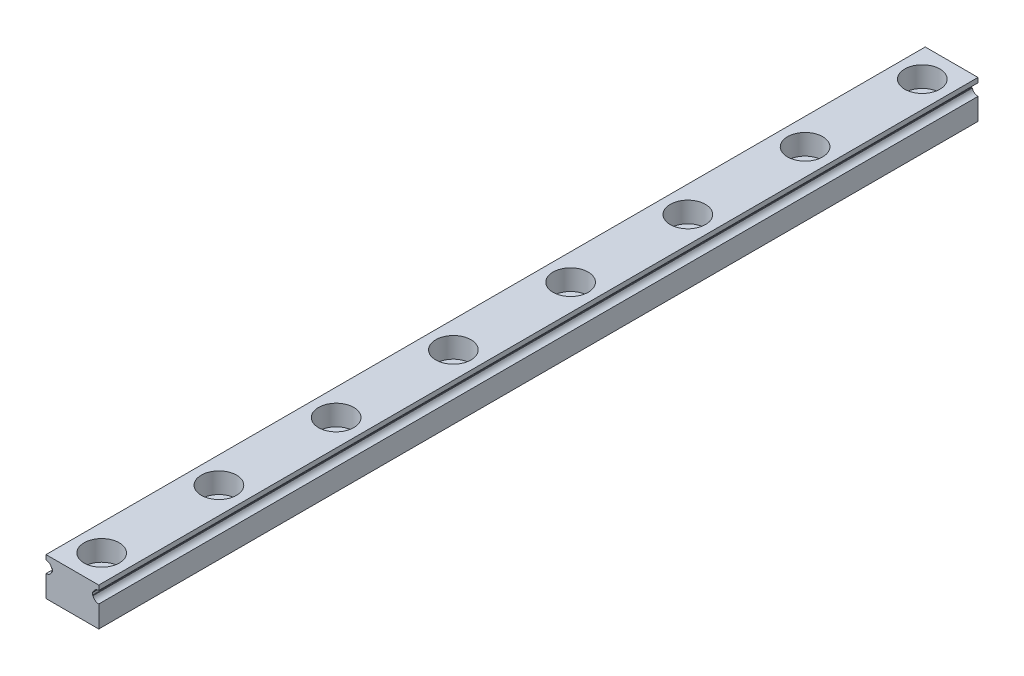
SolidWorks part; units mm, degrees
material "6061 合金"
ref_plane "Спереди" through (0, 0, 0) normal (0, 0, 1) x (1, 0, 0)
ref_plane "Сверху" through (0, 0, 0) normal (0, 1, 0) x (1, 0, 0)
ref_plane "Справа" through (0, 0, 0) normal (1, 0, 0) x (0, 0, -1)
sketch "Sketch1" plane through (0, 0, 0) normal (0, 0, 1) x (1, 0, 0)
  line L0 (0, 0) -> (0, 5.7299) construction
  line L1 (-4.5, -3.25) -> (4.5, -3.25)
  line L2 (-4.5, -3.25) -> (-4.5, 0.45)
  line L3 (-4.5, 3.25) -> (4.5, 3.25)
  line L4 (4.5, -3.25) -> (4.5, 0.45)
  line L5 (-4.5, -3.25) -> (4.5, 3.25) construction
  line L6 (-4.5, 3.25) -> (4.5, -3.25) construction
  line L7 (-4.5, 2.45) -> (-4.5, 3.25)
  line L8 (-3.5318, 1.2) -> (-3.4, 1.2)
  line L9 (3.5318, 1.2) -> (3.4, 1.2)
  line L10 (-3.5318, 1.7) -> (-3.4, 1.7)
  line L11 (-3.4, 1.2) -> (-3.4, 1.7)
  line L12 (3.4, 1.2) -> (3.4, 1.7)
  line L13 (3.5318, 1.7) -> (3.4, 1.7)
  line L14 (4.5, 2.45) -> (4.5, 3.25)
  line L15 (-3.4, 1.45) -> (-4.5, 1.45) construction
  arc A0 (-3.5318, 1.7) -> (-4.5, 2.45) centre (-4.5, 1.45) ccw
  arc A1 (-4.5, 0.45) -> (-3.5318, 1.2) centre (-4.5, 1.45) ccw
  arc A2 (4.5, 0.45) -> (3.5318, 1.2) centre (4.5, 1.45) cw
  arc A3 (3.5318, 1.7) -> (4.5, 2.45) centre (4.5, 1.45) cw
  point P0 (0, 0)
  dimension "D3" = 1
  dimension "D1" = 9
  dimension "D2" = 6.5
  dimension "D4" = 2.05
  dimension "D5" = 6.8
  dimension "D6" = 0.5
extrude "Extrude1" add sketch "Sketch1" along normal blind 150
sketch "Sketch2" plane through (0, 3.25, 0) normal (0, 1, 0) x (1, 0, 0)
  line L0 (4.5, 0) -> (-4.5, 0) construction
  circle A0 centre (0, -5) radius 1.75
  circle A1 centre (0, -5) radius 3
  dimension "D1" = 3.5
  dimension "D2" = 6
  dimension "D3" = 5
extrude "Extrude2" cut sketch "Sketch2" against normal blind 3.5 contours A1
extrude "Extrude3" cut sketch "Sketch" against normal through all contours A0
sketch "Sketch" plane through (0, 3.25, 0) normal (0, 1, 0) x (1, 0, 0) same geometry as "Sketch2"
pattern_linear "LPattern1" count 40 spacing 20 along (0, 0, 1) of "Extrude2", "Extrude3"
chamfer "Chamfer1" [suppressed] distance 0.3 angle 45
sketch "草图1" [suppressed] plane through (0, 0, 200) normal (0, 0, 1) x (1, 0, 0)
  line L12 (4.5, 2.45) -> (4.5, 3.25)
  line L13 (4.5, 3.25) -> (-4.5, 3.25)
  line L14 (-4.5, 3.25) -> (-4.5, 2.45)
  line L15 (-3.5318, 1.7) -> (-3.4, 1.7)
  line L16 (-3.4, 1.7) -> (-3.4, 1.2)
  line L17 (-3.4, 1.2) -> (-3.5318, 1.2)
  line L18 (-4.5, 0.45) -> (-4.5, -3.25)
  line L19 (-4.5, -3.25) -> (4.5, -3.25)
  line L20 (4.5, -3.25) -> (4.5, 0.45)
  line L21 (3.5318, 1.2) -> (3.4, 1.2)
  line L22 (3.4, 1.2) -> (3.4, 1.7)
  line L23 (3.4, 1.7) -> (3.5318, 1.7)
  line L24 (4.5, 2.45) -> (4.5, 3.25)
  line L25 (4.5, 3.25) -> (-4.5, 3.25)
  line L26 (-4.5, 3.25) -> (-4.5, 2.45)
  line L27 (-3.5318, 1.7) -> (-3.4, 1.7)
  line L28 (-3.4, 1.7) -> (-3.4, 1.2)
  line L29 (-3.4, 1.2) -> (-3.5318, 1.2)
  line L30 (-4.5, 0.45) -> (-4.5, -3.25)
  line L31 (-4.5, -3.25) -> (4.5, -3.25)
  line L32 (4.5, -3.25) -> (4.5, 0.45)
  line L33 (3.5318, 1.2) -> (3.4, 1.2)
  line L34 (3.4, 1.2) -> (3.4, 1.7)
  line L35 (3.4, 1.7) -> (3.5318, 1.7)
  arc A4 (-3.5318, 1.7) -> (-4.5, 2.45) centre (-4.5, 1.45) ccw
  arc A5 (-4.5, 0.45) -> (-3.5318, 1.2) centre (-4.5, 1.45) ccw
  arc A6 (3.5318, 1.2) -> (4.5, 0.45) centre (4.5, 1.45) ccw
  arc A7 (4.5, 2.45) -> (3.5318, 1.7) centre (4.5, 1.45) ccw
  arc A8 (-3.5318, 1.7) -> (-4.5, 2.45) centre (-4.5, 1.45) ccw
  arc A9 (-4.5, 0.45) -> (-3.5318, 1.2) centre (-4.5, 1.45) ccw
  arc A10 (3.5318, 1.2) -> (4.5, 0.45) centre (4.5, 1.45) ccw
  arc A11 (4.5, 2.45) -> (3.5318, 1.7) centre (4.5, 1.45) ccw
  dimension "D1" = 0
extrude "切除-拉伸1" [suppressed] cut sketch "草图1" against normal blind 30
